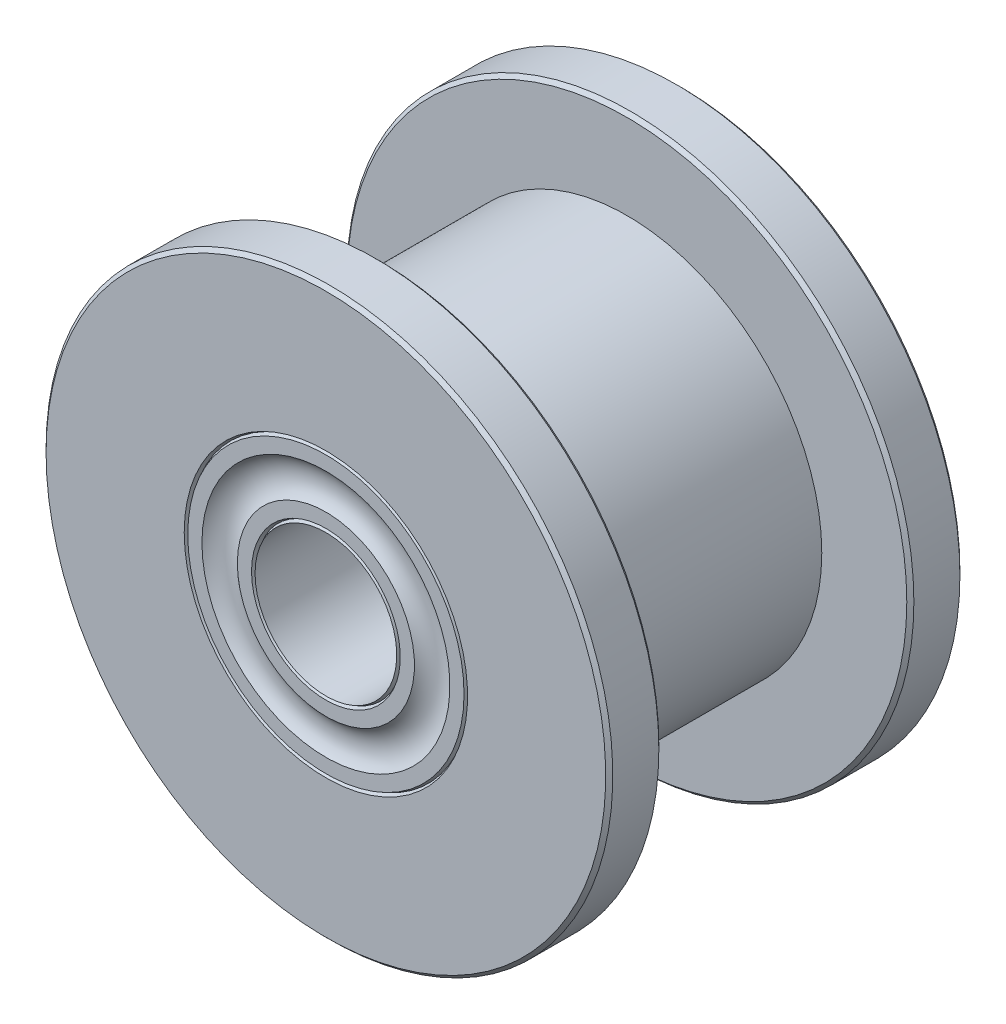
SolidWorks part; units mm, degrees
material "Aleación 1060"
ref_plane "Alzado" through (0, 0, 0) normal (0, 0, 1) x (1, 0, 0)
ref_plane "Planta" through (0, 0, 0) normal (0, 1, 0) x (1, 0, 0)
ref_plane "Vista lateral" through (0, 0, 0) normal (1, 0, 0) x (0, 0, -1)
sketch "Croquis1" plane through (0, 0, 0) normal (0, 0, 1) x (1, 0, 0)
  circle A0 centre (0, 0) radius 5.5
  circle A1 centre (0, 0) radius 2
  dimension "D1" = 11
  dimension "D2" = 4
extrude "Saliente-Extruir1" add sketch "Croquis1" along normal blind 10
sketch "Croquis2" plane through (0, 0, 0) normal (0, 0, 1) x (1, 0, 0)
  circle A0 centre (0, 0) radius 8
  circle A1 centre (0, 0) radius 2
  dimension "D1" = 4
  dimension "D2" = 16
extrude "Saliente-Extruir3" add sketch "Croquis2" along normal blind 1.5
extrude "Saliente-Extruir5" add sketch "Croquis2<3>" along normal blind 1.5 from offset 8.5
sketch "Croquis2<3>" plane through (0, 0, 0) normal (0, 0, 1) x (1, 0, 0) same geometry as "Croquis2"
chamfer "Chaflán1" distance 0.1 angle 45 4 edges at (8, 0, 0) (8, 0, 1.5) (8, 0, 8.5) (8, 0, 10)
sketch "Croquis3" plane through (0, 0, 0) normal (0, 1, 0) x (1, 0, 0)
  line L0 (-2, 0) -> (-2.05, -0.1)
  line L1 (8, -0.1) -> (-8, -0.1) construction
  line L2 (-2.05, -0.1) -> (-2.1, 0)
  line L3 (7.9, 0) -> (-7.9, 0) construction
  line L4 (-3.9, 0) -> (-3.5, 0)
  line L5 (-2.1, 0) -> (-2.5, 0)
  line L6 (-3.9, 0) -> (-3.95, -0.1)
  line L7 (-3.95, -0.1) -> (-4, 0)
  line L8 (-4, 0) -> (-4, 0.1)
  line L9 (-4, 0.1) -> (-2, 0.1)
  line L10 (-2, 0.1) -> (-2, 0)
  line L11 (-4, 0) -> (-3.9, 0) construction
  line L12 (-3.95, 0) -> (-3.95, -0.1) construction
  line L13 (-2.1, 0) -> (-2, 0) construction
  line L14 (-2.05, 0) -> (-2.05, -0.1) construction
  line L15 (0, 0) -> (0, -10) construction
  line L16 (-7.9, -10) -> (7.9, -10) construction
  line L17 (0, -5) -> (-8.0596, -5) construction
  line L18 (-2.05, -10) -> (-2.05, -9.9) construction
  line L19 (-2.1, -10) -> (-2, -10) construction
  line L20 (-3.95, -10) -> (-3.95, -9.9) construction
  line L21 (-4, -10) -> (-3.9, -10) construction
  line L22 (-2, -10.1) -> (-2, -10)
  line L23 (-4, -10.1) -> (-2, -10.1)
  line L24 (-4, -10) -> (-4, -10.1)
  line L25 (-3.95, -9.9) -> (-4, -10)
  line L26 (-3.9, -10) -> (-3.95, -9.9)
  line L27 (-2.1, -10) -> (-2.5, -10)
  line L28 (-3.9, -10) -> (-3.5, -10)
  line L29 (-2.05, -9.9) -> (-2.1, -10)
  line L30 (-2, -10) -> (-2.05, -9.9)
  arc A0 (-3.5, 0) -> (-2.5, 0) centre (-3, 0.4899) ccw
  arc A1 (-3.5, -10) -> (-2.5, -10) centre (-3, -10.4899) cw
  dimension "D5" = 0.7
  dimension "D1" = 0.1
  dimension "D2" = 0.1
  dimension "D3" = 2
  dimension "D4" = 1
  dimension "D6" = 0.1
revolve "Cortar-Revolución1" cut sketch "Croquis3" angle 360 about L15
